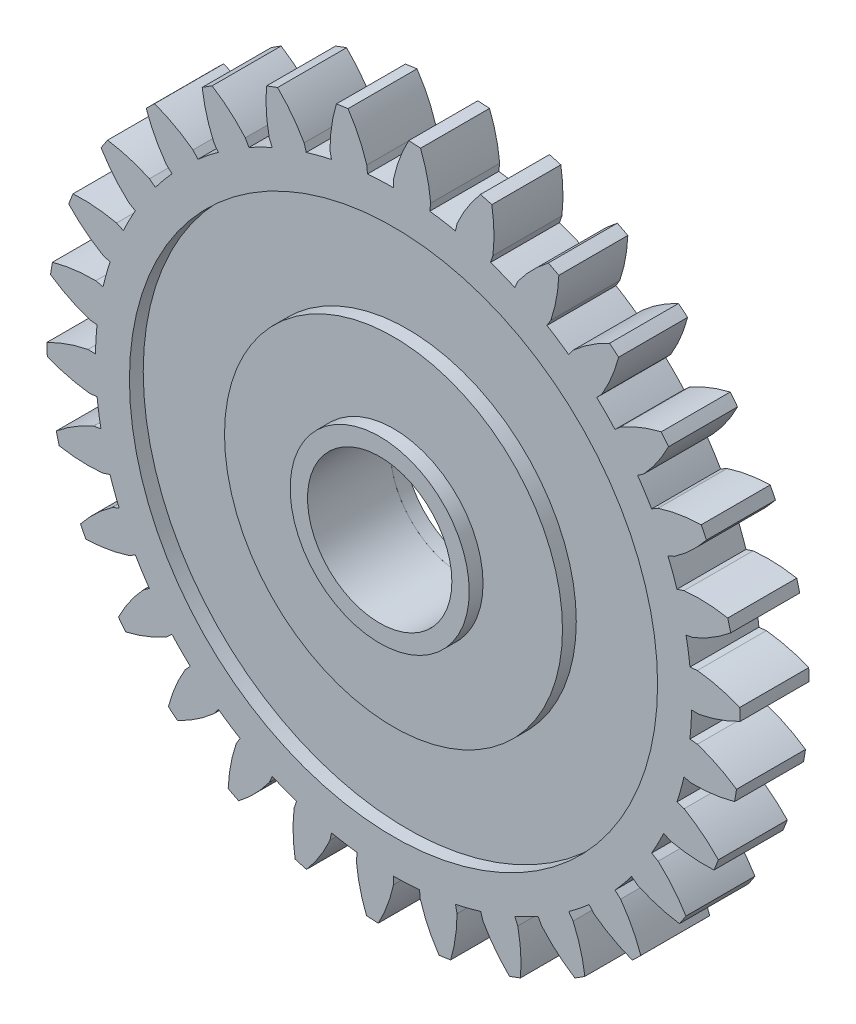
SolidWorks part; units mm, degrees
ref_plane "Front Plane" through (0, 0, 0) normal (0, 0, 1) x (1, 0, 0)
ref_plane "Top Plane" through (0, 0, 0) normal (0, 1, 0) x (1, 0, 0)
ref_plane "Right Plane" through (0, 0, 0) normal (1, 0, 0) x (0, 0, -1)
sketch "Sketch1" plane through (0, 0, 0) normal (0, 0, 1) x (1, 0, 0)
  circle A0 centre (0, 0) radius 47.13
  circle A1 centre (0, 0) radius 50.272
  circle A2 centre (0, 0) radius 43.2025
  circle A3 centre (0, 0) radius 43.988
  circle A4 centre (0, 0) radius 44.2877
  point P13 (0, 0)
  point P16 (0, 0)
  dimension "Pitch" = 94.26
  dimension "Base" = 88.5754
  dimension "Addenum" = 100.544
  dimension "Clearance" = 87.976
  dimension "Root" = 86.405
sketch "Involute" plane through (0, 0, 0) normal (0, 0, 1) x (1, 0, 0)
  line L0 (0, 0) -> (0, 44.2877)
  line L1 (0, 0) -> (22.1439, 38.3543) construction
  line L2 (0, 0) -> (38.3543, 22.1439) construction
  line L3 (0, 0) -> (44.2877, 0) construction
  line L4 (44.2877, 0) -> (44.2877, 69.567) construction
  line L5 (38.3543, 22.1439) -> (15.1653, 62.3084) construction
  line L6 (22.1439, 38.3543) -> (2.0616, 49.9488) construction
  line L7 (0, 0) -> (9.7989, 46.1001)
  line L8 (0, 0) -> (4.9264, 46.8718) construction
  line L9 (2.8719, 47.0424) -> (0, 0) construction
  circle A0 centre (0, 0) radius 44.2877 construction
  circle A1 centre (0, 0) radius 47.13 construction
  arc A4 (4.9264, 46.8718) -> (0.8119, 47.123) centre (0, 0) ccw
  spline S0 degree 3 poles (0, 44.2877) (3.8958, 62.4242) (29.3425, 69.5906) (44.2877, 69.567) knots 0 0 0 0 1 1 1 1
  spline S1 degree 3 poles (5.3874, 43.9588) (3.7268, 62.4345) (-20.6592, 72.6432) (-35.4963, 74.4377) knots 0 0 0 0 1 1 1 1
  dimension "D1" = 90
  dimension "D2" = 69.567
  dimension "D3" = 46.378
  dimension "D4" = 23.189
  dimension "Circular pitch" = 12
sketch "Sketch3" plane through (0, 0, 0) normal (0, 0, 1) x (1, 0, 0)
  line L0 (5.3874, 43.9588) -> (5.2554, 42.8817)
  line L1 (0, 0) -> (0, 44.2877) construction
  line L2 (0, 43.2025) -> (0, 44.2877)
  circle A0 centre (0, 0) radius 43.2025 construction
  circle A2 centre (0, 0) radius 44.2877 construction
  circle A4 centre (0, 0) radius 50.272 construction
  arc A5 (5.2554, 42.8817) -> (0, 43.2025) centre (0, 0) ccw
  arc A7 (5.3874, 43.9588) -> (0, 44.2877) centre (0, 0) ccw
  arc A9 (3.917, 50.1192) -> (2.2089, 50.2234) centre (0, 0) ccw
  circle A10 centre (0, 0) radius 43.2025
  spline S4 degree 3 poles (0, 44.2877) (0.457, 46.4152) (1.2105, 48.3918) (2.2089, 50.2234) knots 0 0 0 0 0.117305 0.117305 0.117305 0.117305
  spline S5 degree 3 poles (5.3874, 43.9588) (5.1926, 46.1261) (4.6851, 48.1796) (3.917, 50.1192) knots 0 0 0 0 0.117305 0.117305 0.117305 0.117305
extrude "Boss-Extrude1" add sketch "Sketch3" along normal blind 10 contours A7 S5 A9 S4 | L0 A7 L2 A5 region at (2.6641, 43.639, 0) region at (2.8512, 46.7029, 0)
ref_axis "Axis1" through (0, 0, 0) along (0, 0, 1)
pattern_circular "CirPattern1" count 30 over 360 about axis through (0, 0, 0) along (0, 0, 1) of bodies 101
extrude "Boss-Extrude2" add sketch "Sketch1" along normal blind 10 contours A2 region at (0, 0, 0)
sketch "Sketch4" plane through (0, 0, 10) normal (0, 0, 1) x (1, 0, 0)
  circle A0 centre (0, 0) radius 38.2772
  circle A1 centre (0, 0) radius 24.4944
  circle A2 centre (0, 0) radius 12.9802
  circle A3 centre (0, 0) radius 10.4586
extrude "Cut-Extrude1" cut sketch "Sketch4" against normal blind 2 contours A0 A1 region at (-37.1945, 0, 10)
extrude "Cut-Extrude2" cut sketch "Sketch4<3>" against normal through all contours A3 region at (0, 0, 10)
sketch "Sketch4<3>" plane through (0, 0, 10) normal (0, 0, 1) x (1, 0, 0) same geometry as "Sketch4"
ref_plane "Plane1" through (0, 0, 5) normal (0, 0, 1) x (1, 0, 0)
extrude "Boss-Extrude3" add sketch "Sketch4<4>" along normal blind 2 contours A2 A3 region at (-12.613, 0, 10)
sketch "Sketch4<4>" plane through (0, 0, 10) normal (0, 0, 1) x (1, 0, 0) same geometry as "Sketch4"
sketch "Sketch5" plane through (0, 0, 0) normal (0, 0, -1) x (-1, 0, 0)
  circle A1 centre (0, 0) radius 10.4586
  circle A2 centre (0, 0) radius 10.4586
  circle A3 centre (0, 0) radius 12.9802
  circle A4 centre (0, 0) radius 12.9802
  circle A5 centre (0, 0) radius 24.4944
  circle A6 centre (0, 0) radius 24.4944
  circle A7 centre (0, 0) radius 38.2772
  circle A8 centre (0, 0) radius 38.2772
  dimension "D1" = 0
  dimension "D2" = 0
  dimension "D3" = 0
  dimension "D4" = 0
extrude "Cut-Extrude3" cut sketch "Sketch5" against normal blind 2 contours A8 A6 region at (37.1945, 0, 0)
extrude "Boss-Extrude4" add sketch "Sketch5<3>" along normal blind 2 separate body contours A4 A2 region at (12.613, 0, 0)
sketch "Sketch5<3>" plane through (0, 0, 0) normal (0, 0, -1) x (-1, 0, 0) same geometry as "Sketch5"
equation "\"Modules\" = 3.142"
equation "\"No of teeth\" =30"
equation "\"Pressure angle\" = 20deg"
equation "\"Addenum@Sketch1\"= \"Pitch@Sketch1\" + ( \"Modules\" * 2 )"
equation "\"Clearance@Sketch1\"= \"Pitch@Sketch1\" - ( \"Modules\" * 2 )"
equation "\"Pitch@Sketch1\"= \"Modules\" * \"No of teeth\""
equation "\"Root@Sketch1\"= \"Pitch@Sketch1\" - ( ( \"Modules\" * 1.25 ) * 2 )"
equation "\"Base@Sketch1\"= \"Pitch@Sketch1\" * cos ( \"Pressure angle\" )"
equation "\"Circular pitch@Involute\"=360/\"No of teeth\""
equation "\"D1@CirPattern1\"=\"No of teeth\""
